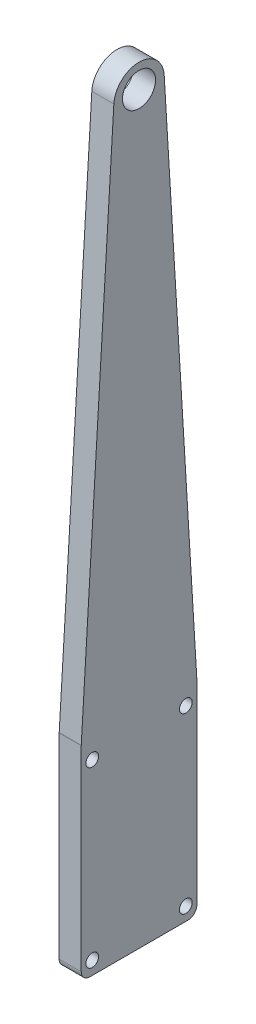
SolidWorks part; units mm, degrees
material "6061 Alloy"
ref_plane "Front Plane" through (0, 0, 0) normal (0, 0, 1) x (1, 0, 0)
ref_plane "Top Plane" through (0, 0, 0) normal (0, 1, 0) x (1, 0, 0)
ref_plane "Right Plane" through (0, 0, 0) normal (1, 0, 0) x (0, 0, -1)
sketch "Sketch1" plane through (0, 0, 0) normal (1, 0, 0) x (0, 0, -1)
  line L0 (-13.4747, 0) -> (13.4747, 0) construction
  line L1 (0, 0) -> (0, 160) construction
  line L2 (-13.4747, 0) -> (0, 160) construction
  line L3 (0, 160) -> (13.4747, 0) construction
  line L4 (13.4747, 0) -> (-13.4747, 0) construction
  line L8 (-13.4747, 0) -> (13.4747, 0) construction
  line L9 (-13.4747, 0) -> (-13.4747, -50) construction
  line L10 (13.4747, 0) -> (13.4747, -50) construction
  line L11 (-13.4747, -50) -> (13.4747, -50) construction
  line L16 (-16.645, -53.81) -> (16.645, -53.81)
  line L17 (-16.645, -53.81) -> (-16.645, 5.15)
  line L18 (16.645, -53.81) -> (16.645, 5.15)
  line L19 (-16.645, 5.15) -> (16.645, 5.15)
  line L20 (-16.645, 5.15) -> (-7.2492, 160.4386)
  line L21 (-7.2492, 160.4386) -> (7.2492, 160.4386) construction
  line L22 (7.2492, 160.4386) -> (16.645, 5.15)
  circle A0 centre (-13.4747, 0) radius 1.8288
  circle A1 centre (0, 160) radius 4.7625 construction
  circle A2 centre (13.4747, 0) radius 1.8288
  circle A3 centre (-13.4747, -50) radius 1.8288
  circle A4 centre (13.4747, -50) radius 1.8288
  arc A5 (-7.2492, 160.4386) -> (7.2492, 160.4386) centre (0, 160) cw
  point P4 (0, 0)
  point P7 (0, -53.81)
  dimension "D3" = 3.6576
  dimension "D4" = 9.525
  dimension "D9" = 2.5
  dimension "D1" = 26.9494
  dimension "D5" = 50
  dimension "D6" = 3.81
  dimension "D7" = 160
  dimension "D8" = 5.15
  dimension "D2" = 33.29
extrude "Boss-Extrude1" add sketch "Sketch1" along normal mid plane 6.35 contours A5 L20 L19 L22 | L19 L17 L16 L18 A4 A3 A2 A0 region at (0, -24.3153, 0) region at (0, 74.449, 0)
sketch "Sketch2" plane through (3.175, 0, 0) normal (1, 0, 0) x (0, 0, -1)
  line L3 (-11.645, -47.5) -> (-11.645, -2.5)
  line L4 (11.645, -47.5) -> (11.645, -2.5)
  line L5 (-11.645, -2.5) -> (11.645, -2.5)
  line L6 (-11.645, -47.5) -> (11.645, -47.5)
  line L7 (-11.645, -47.5) -> (11.645, -2.5) construction
  line L8 (-16.645, -53.81) -> (-16.645, 5.15) construction
  line L15 (11.645, -47.5) -> (-11.645, -2.5) construction
  line L24 (16.645, -53.81) -> (16.645, 5.15) construction
  line L31 (11.645, -44.7805) -> (-10.2375, -2.5)
  line L32 (-10.2375, -47.5) -> (11.645, -5.2195)
  line L33 (10.2375, -47.5) -> (-11.645, -5.2195)
  line L34 (-11.645, -44.7805) -> (10.2375, -2.5)
  line L35 (12.7551, -46.9254) -> (-10.5349, -1.9254) construction
  line L36 (10.5349, -48.0746) -> (-12.7551, -3.0746) construction
  line L37 (-10.5349, -48.0746) -> (12.7551, -3.0746) construction
  line L38 (-12.7551, -46.9254) -> (10.5349, -1.9254) construction
  circle A0 centre (13.4747, -50) radius 1.8288 construction
  circle A1 centre (13.4747, 0) radius 1.8288 construction
  point P0 (11.645, -25)
  point P2 (0, -47.5)
  point P28 (0, -25)
  dimension "D4" = 2.5
  dimension "D1" = 5
  dimension "D2" = 5
  dimension "D3" = 2.5
  dimension "D5" = 1.25
  dimension "D6" = 1.25
extrude "Cut-Extrude1" [suppressed] cut sketch "Sketch2" against normal through all contours L32 L31 L4 | L6 L33 L32 | L3 L34 L33 | L31 L34 L5
fillet "Fillet1" [suppressed] radius 2.5
fillet "Fillet2" radius 2.5 4 edges at (0, 5.15, 16.645) (0, 5.15, -16.645) (0, -53.81, -16.645) (0, -53.81, 16.645)
hole_wizard "3/8 (0.3750) Dowel Hole1" positions "Sketch3" profile "Sketch4" hole size "3/8" standard "ANSI Inch" end condition through all
sketch "Sketch3" plane through (3.175, 0, 0) normal (1, 0, 0) x (0, 0, -1)
  line L0 (-7.2492, 160.4386) -> (7.2492, 160.4386) construction
  point P0 (0, 160.4386)
sketch "Sketch4" plane through (3.175, 160.4386, 0) normal (0, 1, 0) x (0, 0, -1)
  line L0 (0, 0) -> (0, 6.35)
  line L1 (0, 6.35) -> (4.7625, 6.35)
  line L2 (4.7625, 6.35) -> (4.7625, 0)
  line L5 (4.7625, 0) -> (0, 0)
  line L11 (0, -6.35) -> (0, 107.95) construction
  dimension "Thru Hole Dia." = 9.525
  dimension "Thru Hole Depth" = 6.35
